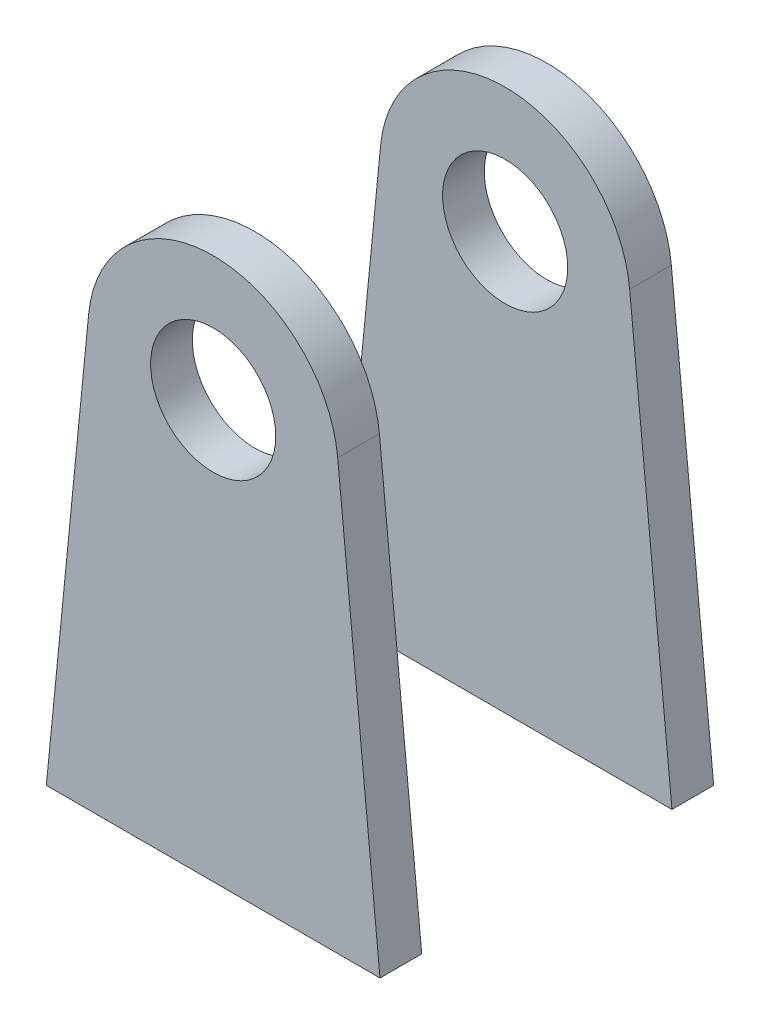
SolidWorks part; units mm, degrees
ref_plane "Front Plane" through (0, 0, 0) normal (0, 0, 1) x (1, 0, 0)
ref_plane "Top Plane" through (0, 0, 0) normal (0, 1, 0) x (1, 0, 0)
ref_plane "Right Plane" through (0, 0, 0) normal (1, 0, 0) x (0, 0, -1)
sketch "Sketch1" plane through (0, 0, 0) normal (0, 0, 1) x (1, 0, 0)
  line L0 (0, 0) -> (0, -31.75) construction
  line L1 (-9.4791, 0.9341) -> (-12.7, -31.75)
  line L2 (9.4791, 0.9341) -> (12.7, -31.75)
  line L3 (-12.7, -31.75) -> (12.7, -31.75)
  circle A0 centre (0, 0) radius 4.7625
  circle A1 centre (0, 0) radius 9.525
  dimension "D1" = 25.4
  dimension "D2" = 9.525
  dimension "D4" = 19.05
  dimension "D3" = 31.75
extrude "Boss-Extrude1" add sketch "Sketch1" against normal blind 3.175 from offset 12.7 contours A0 A1 | L0 A1 L1 | A1 L0 L2 region at (0, -19.7917, 0) region at (0, 9.2556, 0)
extrude "Boss-Extrude2" add sketch "Sketch1<4>" along normal blind 3.175 from offset 12.7 separate body contours A0 A1 | A1 L0 L2 | L0 A1 L1 region at (0, -19.7917, 0) region at (0, 9.2556, 0) offset against normal yes
sketch "Sketch1<4>" plane through (0, 0, 0) normal (0, 0, 1) x (1, 0, 0) same geometry as "Sketch1"
